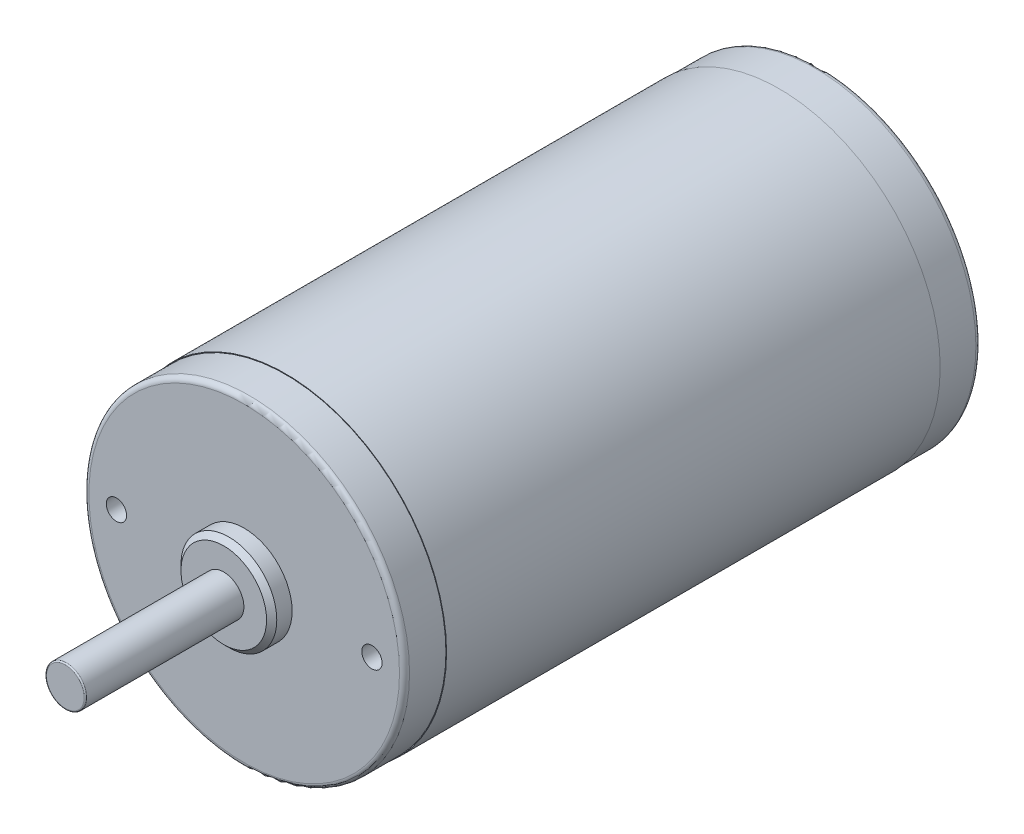
SolidWorks part; units mm, degrees
ref_plane "Front Plane" through (0, 0, 0) normal (0, 0, 1) x (1, 0, 0)
ref_plane "Top Plane" through (0, 0, 0) normal (0, 1, 0) x (1, 0, 0)
ref_plane "Right Plane" through (0, 0, 0) normal (1, 0, 0) x (0, 0, -1)
ref_plane "Plane1" through (0, 109.2962, 0) normal (0, -1, 0) x (1, 0, 0)
sketch "Sketch1" plane through (0, 109.2962, 0) normal (0, -1, 0) x (1, 0, 0)
  line L0 (67.564, 10.8204) -> (35.56, 10.8204)
  line L1 (35.56, 10.8204) -> (35.56, -87.3252)
  line L2 (35.56, -87.3252) -> (67.564, -87.3252)
  line L3 (67.564, -87.3252) -> (67.564, 10.8204)
  line L4 (35.56, 10.8204) -> (35.56, -87.3252) construction
revolve "Revolve1" add sketch "Sketch1" angle 360 about L4 reverse direction yes
sketch "Sketch2" plane through (0, 0, 10.8204) normal (0, 0, 1) x (1, 0, 0)
  circle A0 centre (35.56, 109.2962) radius 31.877
extrude "Boss-Extrude1" add sketch "Sketch2" along normal blind 8.2296
ref_plane "Plane2" through (0, 0, 18.542) normal (0, 0, -1) x (-1, 0, 0)
sketch "Sketch5" plane through (0, 0, 18.542) normal (0, 0, -1) x (-1, 0, 0)
  circle A0 centre (-35.56, 109.2962) radius 9.525
extrude "Boss-Extrude2" add sketch "Sketch5" against normal blind 4.572
sketch "Sketch6" plane through (0, 0, 23.114) normal (0, 0, 1) x (1, 0, 0)
  circle A0 centre (35.56, 109.2962) radius 4
extrude "Boss-Extrude3" add sketch "Sketch6" along normal blind 31.5
sketch "Sketch8" plane through (0, 0, -87.3252) normal (0, 0, -1) x (-1, 0, 0)
  circle A0 centre (-35.56, 109.2962) radius 31.877
extrude "Boss-Extrude4" add sketch "Sketch8" along normal blind 8.2296
sketch "Sketch9" plane through (0, 0, -95.5548) normal (0, 0, -1) x (-1, 0, 0)
  circle A0 centre (-35.56, 109.2962) radius 15.0368
extrude "Boss-Extrude5" add sketch "Sketch9" along normal blind 4.7625
ref_plane "Plane3" [suppressed] through (0, 120.5036, 0) normal (0, 1, 0) x (-1, 0, 0)
ref_plane "Plane4" [suppressed] through (0, 127.9033, 0) normal (0, 1, 0) x (-1, 0, 0)
hole_wizard "Hole2" positions "Sketch13" profile "Sketch12" legacy
sketch "Sketch13" plane through (0, 0, 19.05) normal (0, 0, 1) x (1, 0, 0)
  point P0 (60.96, 109.2962)
sketch "Sketch12" plane through (60.96, 109.2962, 19.05) normal (1, 0, 0) x (0, -1, 0)
  line L0 (0, 0) -> (0, 14.8277)
  line L1 (0, 14.8277) -> (2.0193, 13.6144)
  line L2 (2.0193, 13.6144) -> (2.0193, 0)
  line L4 (2.0193, 0) -> (0, 0)
  line L6 (0, 14.8277) -> (-2.0193, 13.6144) construction
  line L7 (0, -4.2442) -> (0, 117.3081) construction
  dimension "Diameter" = 4.0386
  dimension "Depth" = 13.6144
  dimension "Drill Angle" = 118
hole_wizard "Hole3" positions "Sketch15" profile "Sketch14" legacy
sketch "Sketch15" plane through (0, 0, 19.05) normal (0, 0, 1) x (1, 0, 0)
  point P0 (10.16, 109.2962)
sketch "Sketch14" plane through (10.16, 109.2962, 19.05) normal (1, 0, 0) x (0, -1, 0)
  line L0 (0, 0) -> (0, 14.8277)
  line L1 (0, 14.8277) -> (2.0193, 13.6144)
  line L2 (2.0193, 13.6144) -> (2.0193, 0)
  line L4 (2.0193, 0) -> (0, 0)
  line L6 (0, 14.8277) -> (-2.0193, 13.6144) construction
  line L7 (0, -4.2442) -> (0, 117.3081) construction
  dimension "Diameter" = 4.0386
  dimension "Depth" = 13.6144
  dimension "Drill Angle" = 118
chamfer "Chamfer1" distance 1.016 angle 45 1 edges at (45.085, 109.2962, 23.114) first distance on face at (45.085, 109.2962, 23.114)
fillet "Fillet1" radius 0.254 1 edges at (39.56, 109.2962, 54.614) tangent propagation no
fillet "Fillet2" radius 1 1 edges at (3.683, 109.2962, -95.5548) tangent propagation no
fillet "Fillet3" radius 1 1 edges at (67.437, 109.2962, 19.05) tangent propagation no
fillet "Fillet4" radius 1 1 edges at (20.5232, 109.2962, -100.3173) tangent propagation no
ref_plane "Plane5" [suppressed] through (39.56, 0, 0) normal (1, 0, 0) x (0, 0, -1)
ref_axis "Centerline" through (35.56, 109.2962, 74.6926) along (0, 0, -1)
ref_axis "Mounting Axis" through (60.96, 109.2962, 5.4356) along (0, 0, 1)
ref_plane "MidPlane" through (0, 109.2962, 0) normal (0, -1, 0) x (-1, 0, 0)
